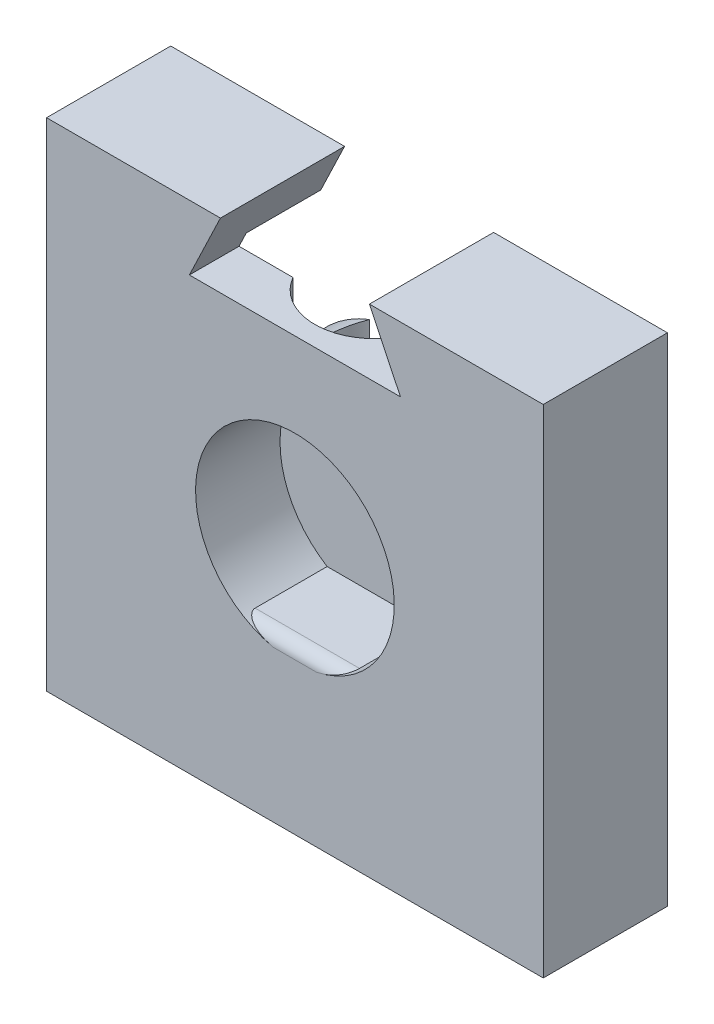
SolidWorks part; units mm, degrees
ref_plane "Front Plane" through (0, 0, 0) normal (0, 0, 1) x (1, 0, 0)
ref_plane "Top Plane" through (0, 0, 0) normal (0, 1, 0) x (1, 0, 0)
ref_plane "Right Plane" through (0, 0, 0) normal (1, 0, 0) x (0, 0, -1)
sketch "Sketch2" plane through (0, 0, 0) normal (0, 0, 1) x (1, 0, 0)
  line L0 (59.3211, -25.0679) -> (59.3211, -225.0679)
  line L1 (59.3211, -225.0679) -> (-140.6789, -225.0679)
  line L2 (-140.6789, -225.0679) -> (-140.6789, -25.0679)
  line L3 (-140.6789, -25.0679) -> (59.3211, -25.0679)
extrude "Boss-Extrude1" add sketch "Sketch2" against normal blind 50 contours L2 L3 L0 L1
shell "Shell1" thickness 20 removed face at (-40.6789, -125.0679, -50)
sketch "Sketch3" plane through (0, 0, 0) normal (0, 0, 1) x (1, 0, 0)
  line L0 (-10.6789, -25.0679) -> (1.8211, -51.1576)
  line L1 (-70.6789, -25.0679) -> (-140.6789, -25.0679) construction
  line L2 (-10.6789, -25.0679) -> (59.3211, -25.0679) construction
  line L3 (1.8211, -51.1576) -> (-83.1789, -51.1576)
  line L4 (-83.1789, -51.1576) -> (-70.6789, -25.0679)
  line L5 (-140.6789, -25.0679) -> (59.3211, -25.0679) construction
  line L6 (-70.6789, -25.0679) -> (-10.6789, -25.0679)
extrude "Cut-Extrude1" cut sketch "Sketch3" against normal blind 50
sketch "Sketch5" plane through (0, 0, -20) normal (0, 0, -1) x (-1, 0, 0)
  circle A0 centre (40.6789, -125.0679) radius 50
extrude "Boss-Extrude2" add sketch "Sketch5" along normal blind 28
sketch "Sketch6" plane through (0, 0, 0) normal (0, 0, 1) x (1, 0, 0)
  circle A0 centre (-40.6789, -125.0679) radius 40
  circle A1 centre (-40.6789, -125.0679) radius 50 construction
extrude "Cut-Extrude2" cut sketch "Sketch6" against normal blind 34
sketch "Sketch7" plane through (0, -45.0679, 0) normal (0, -1, 0) x (-1, 0, 0)
  line L0 (1.0966, 50) -> (80.2613, 50) construction
  line L1 (80.2613, 50) -> (80.2613, 20) construction
  line L2 (40.6789, 32) -> (80.2613, 35) construction
  line L3 (40.6789, 32) -> (40.6789, 50) construction
  line L4 (1.0966, 50) -> (1.0966, 20) construction
  line L5 (40.6789, 32) -> (1.0966, 35) construction
  circle A0 centre (40.6789, 32) radius 24
extrude "Cut-Extrude4" cut sketch "Sketch7" along normal blind 50 contours A0
sketch "Sketch8" plane through (0, 0, -34) normal (0, 0, 1) x (1, 0, 0)
  line L0 (-61.7024, -159.0975) -> (-19.6555, -159.0975)
  line L1 (-19.6555, -159.0975) -> (-19.6555, -169.0975)
  line L2 (-19.6555, -169.0975) -> (-61.7024, -169.0975)
  line L3 (-61.7024, -169.0975) -> (-61.7024, -159.0975)
  arc A0 (-64.5955, -93.0055) -> (-16.7624, -93.0055) centre (-40.6789, -125.0679) ccw construction
  point P2 (-74.1183, -147.0181)
  point P8 (-6.4282, -134.6444)
  point P9 (-5.3166, -143.7629)
  point P10 (0, 0)
  point P11 (0, 0)
  point P12 (-60.7145, -159.6884)
  point P13 (0, 0)
  point P14 (-61.7024, -172.8685)
  point P15 (0, 0)
extrude "Boss-Extrude3" add sketch "Sketch8" along normal blind 34 contours L0 L1 L2 L3
fillet "Fillet2" radius 5 1 edges at (-40.6789, -159.0975, 0)
